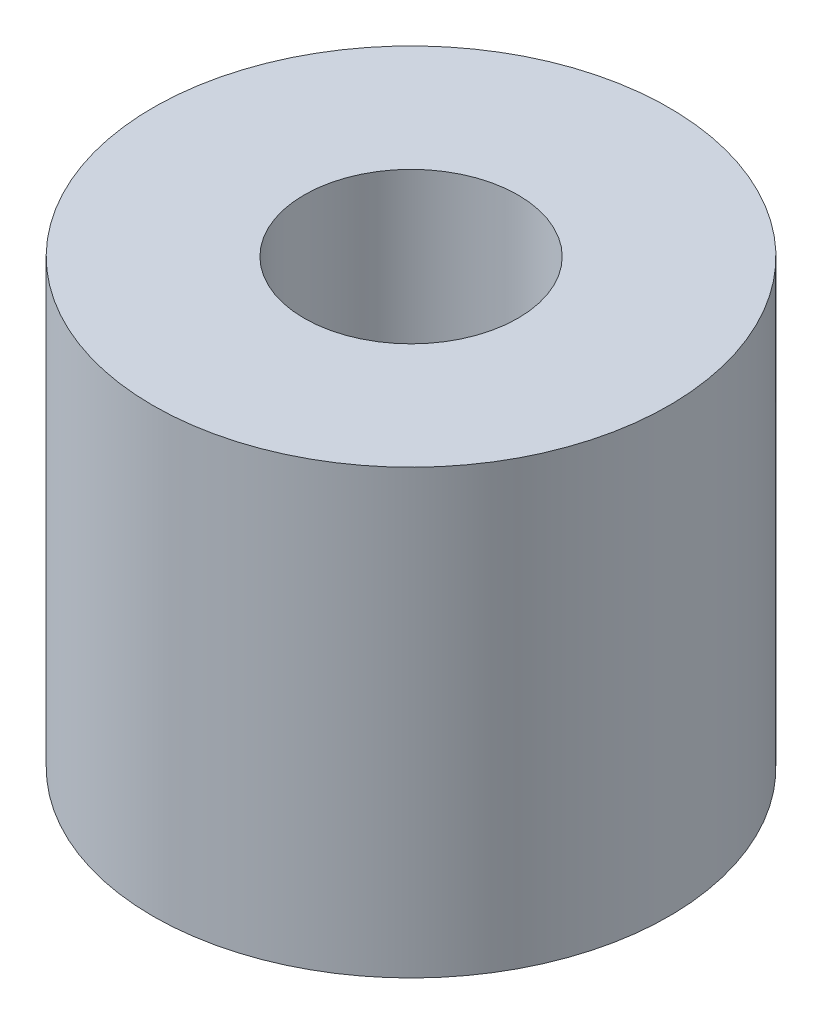
SolidWorks part; units mm, degrees
ref_plane "Front Plane" through (0, 0, 0) normal (0, 0, 1) x (1, 0, 0)
ref_plane "Top Plane" through (0, 0, 0) normal (0, 1, 0) x (1, 0, 0)
ref_plane "Right Plane" through (0, 0, 0) normal (1, 0, 0) x (0, 0, -1)
sketch "Sketch1" plane through (0, 0, 0) normal (0, 1, 0) x (1, 0, 0)
  circle A0 centre (0, 0) radius 3.5
  dimension "D1" = 7
extrude "Boss-Extrude1" add sketch "Sketch1" along normal blind 6
hole_wizard "M2.5 Clearance Hole1" positions "3DSketch1" profile "Sketch2" hole size "M2.5" standard "DIN" end condition through all
sketch3d "3DSketch1"
  line L0 (0, 6, 0) -> (0, 0, 0) construction
  point P0 (0, 6, 0)
sketch "Sketch2" plane through (0, 6, 0) normal (1, 0, 0) x (0, 0, 1)
  line L0 (0, 0) -> (0, 6)
  line L1 (0, 6) -> (1.45, 6)
  line L2 (1.45, 6) -> (1.45, 0)
  line L5 (1.45, 0) -> (0, 0)
  line L11 (0, -6.35) -> (0, 107.95) construction
  dimension "Thru Hole Dia." = 2.9
  dimension "Thru Hole Depth" = 6
